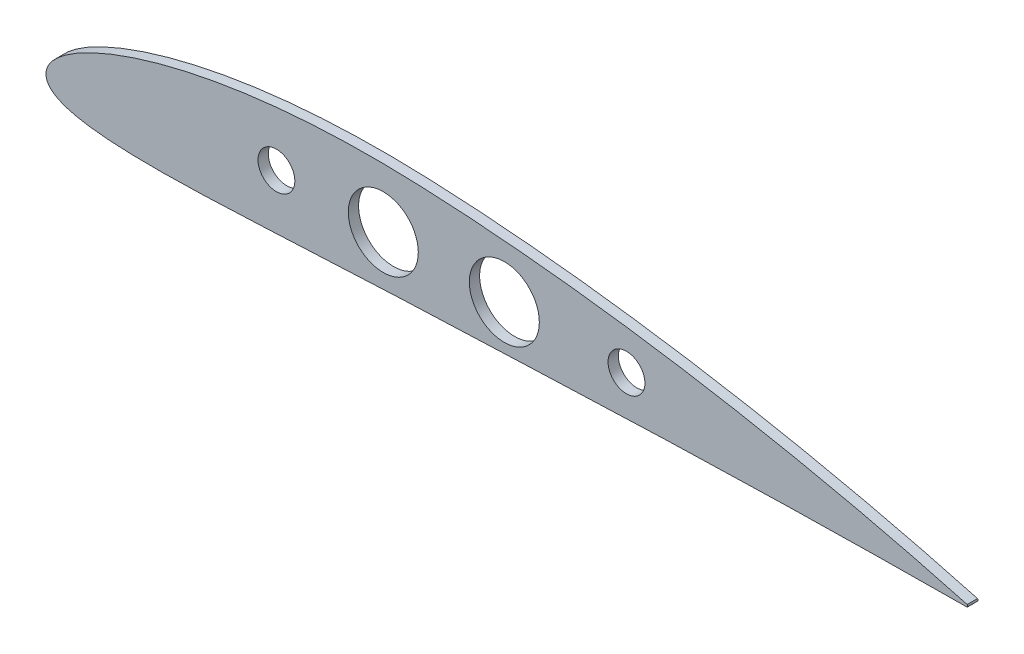
SolidWorks part; units mm, degrees
material "Фанера"
ref_plane "Front Plane" through (0, 0, 0) normal (0, 0, 1) x (1, 0, 0)
ref_plane "Top Plane" through (0, 0, 0) normal (0, 1, 0) x (1, 0, 0)
ref_plane "Right Plane" through (0, 0, 0) normal (1, 0, 0) x (0, 0, -1)
curve "Кривая5"
  spline degree 3 poles (0.048, 0.6214, 0) (0.0227, 0.3735, 0) (-0.0278, -0.1225, 0) (0.078, -0.8844, 0) (0.3497, -1.6388, 0) (0.8143, -2.3651, 0) (1.4635, -3.0393, 0) (2.291, -3.661, 0) (3.3059, -4.2358, 0) (4.5353, -4.7737, 0) (6.0297, -5.2822, 0) (7.869, -5.7653, 0) (10.1688, -6.2217, 0) (13.0754, -6.6396, 0) (16.7281, -6.993, 0) (21.19, -7.2473, 0) (26.4, -7.3766, 0) (32.1974, -7.3763, 0) (38.3978, -7.2614, 0) (44.8576, -7.0566, 0) (51.4865, -6.7865, 0) (58.231, -6.4723, 0) (65.0521, -6.1329, 0) (71.9108, -5.784, 0) (78.7714, -5.4397, 0) (85.6105, -5.111, 0) (92.4321, -4.805, 0) (99.255, -4.532, 0) (106.0974, -4.2783, 0) (112.9692, -4.0031, 0) (119.8644, -3.7232, 0) (126.7739, -3.4401, 0) (133.6816, -3.1587, 0) (140.5819, -2.8824, 0) (147.472, -2.6139, 0) (154.3526, -2.3556, 0) (161.225, -2.1094, 0) (168.0909, -1.8766, 0) (174.9516, -1.6586, 0) (181.8086, -1.4564, 0) (188.6632, -1.2704, 0) (195.5166, -1.1011, 0) (202.3695, -0.9486, 0) (209.2212, -0.8129, 0) (216.0668, -0.6936, 0) (222.8864, -0.5903, 0) (229.6176, -0.5029, 0) (236.0874, -0.4315, 0) (241.9808, -0.3765, 0) (246.559, -0.3395, 0) (249.1205, -0.3213, 0) (250, -0.315, 0) knots 0 0 0 0 0.002941 0.005884 0.009016 0.012365 0.016008 0.020037 0.024574 0.029784 0.035897 0.04324 0.052276 0.063635 0.077983 0.095698 0.11652 0.139661 0.164312 0.189919 0.216157 0.242838 0.269834 0.296993 0.324123 0.351139 0.378036 0.404946 0.431961 0.459078 0.486347 0.513641 0.540929 0.568176 0.59538 0.622543 0.649673 0.676775 0.703855 0.730919 0.757971 0.785018 0.812062 0.839103 0.866132 0.893099 0.919831 0.94581 0.969681 0.98959 1 1 1 1
curve "Кривая6"
  spline degree 3 poles (250, 0.315, 0) (249.1557, 0.545, 0) (246.7202, 1.2085, 0) (242.3913, 2.3583, 0) (236.8498, 3.7876, 0) (230.7799, 5.298, 0) (224.4559, 6.8129, 0) (218.0305, 8.2916, 0) (211.5624, 9.7197, 0) (205.0724, 11.0924, 0) (198.568, 12.4079, 0) (192.0524, 13.6653, 0) (185.5276, 14.8641, 0) (178.9953, 16.0034, 0) (172.4571, 17.0824, 0) (165.9143, 18.0998, 0) (159.3687, 19.0545, 0) (152.8218, 19.9449, 0) (146.2754, 20.7693, 0) (139.7314, 21.5257, 0) (133.1918, 22.212, 0) (126.6587, 22.8257, 0) (120.1368, 23.364, 0) (113.6286, 23.8247, 0) (107.1527, 24.2002, 0) (100.7411, 24.4984, 0) (94.4118, 24.6866, 0) (88.1559, 24.7401, 0) (81.949, 24.6588, 0) (75.7805, 24.441, 0) (69.6537, 24.0819, 0) (63.5754, 23.578, 0) (57.5552, 22.9249, 0) (51.6058, 22.1191, 0) (45.7444, 21.1566, 0) (39.9959, 20.0354, 0) (34.3979, 18.7563, 0) (29.0104, 17.3276, 0) (23.9258, 15.7719, 0) (19.2707, 14.1343, 0) (15.1791, 12.4833, 0) (11.7405, 10.8956, 0) (8.9594, 9.4296, 0) (6.7609, 8.1086, 0) (5.0337, 6.9246, 0) (3.6717, 5.8542, 0) (2.5921, 4.8713, 0) (1.7382, 3.9526, 0) (1.0699, 3.0809, 0) (0.5716, 2.2416, 0) (0.2158, 1.4308, 0) (0.1023, 0.8832, 0) (0.048, 0.6214, 0) knots 0 0 0 0 0.010162 0.029313 0.052012 0.076619 0.101948 0.127526 0.153184 0.178868 0.204558 0.230246 0.255926 0.281594 0.307246 0.332878 0.358485 0.384061 0.409603 0.435104 0.460559 0.485959 0.511303 0.536552 0.561723 0.586629 0.611085 0.635251 0.659272 0.683164 0.706922 0.730536 0.753983 0.777235 0.800246 0.822951 0.845237 0.866916 0.887662 0.906968 0.924203 0.938879 0.950932 0.960693 0.968647 0.975233 0.980795 0.985584 0.989782 0.993521 0.996902 1 1 1 1
sketch "Эскиз1" plane through (0, 0, 0) normal (0, 0, 1) x (1, 0, 0)
  line L0 (250.1305, 0) -> (250.1305, 54.8427) construction
  line L1 (0, 0) -> (0, 70.5199) construction
  line L2 (0, 0) -> (253.0634, 0) construction
  line L3 (62.5326, 62.6361) -> (62.5326, -41.5636) construction
  line L4 (157.5326, 67.9319) -> (157.5326, -57.0034) construction
  line L5 (175.0913, 63.8571) -> (175.0913, -32.3947) construction
  arc A0 (250, 0.315) -> (250, -0.315) centre (249.685, 0) cw
  circle A1 centre (62.5326, 8.5962) radius 5
  circle A2 centre (157.5326, 8.5962) radius 5
  circle A3 centre (91.5326, 8.5962) radius 9.5
  circle A4 centre (124.3816, 8.5962) radius 9.5
  spline S0 degree 3 poles (-1998.9862, 52.2873) (51.3697, 19.9849) (-1.4299, 9.9734) (0.078, -0.8844) (0.3497, -1.6388) (0.8143, -2.3651) (1.4635, -3.0393) (2.291, -3.661) (3.3059, -4.2358) (4.5353, -4.7737) (6.0297, -5.2822) (7.869, -5.7653) (10.1688, -6.2217) (13.0754, -6.6396) (16.7281, -6.993) (21.19, -7.2473) (26.4, -7.3766) (32.1974, -7.3763) (38.3978, -7.2614) (44.8576, -7.0566) (51.4865, -6.7865) (58.231, -6.4723) (65.0521, -6.1329) (71.9108, -5.784) (78.7714, -5.4397) (85.6105, -5.111) (92.4321, -4.805) (99.255, -4.532) (106.0974, -4.2783) (112.9692, -4.0031) (119.8644, -3.7232) (126.7739, -3.4401) (133.6816, -3.1587) (140.5819, -2.8824) (147.472, -2.6139) (154.3526, -2.3556) (161.225, -2.1094) (168.0909, -1.8766) (174.9516, -1.6586) (181.8086, -1.4564) (188.6632, -1.2704) (195.5166, -1.1011) (202.3695, -0.9486) (211.4992, -0.7677) (220.6031, -0.6199) (229.6176, -0.5029) (236.0874, -0.4315) (241.9808, -0.3765) (412.2827, 0.9993) (580.6451, -8.1221) (733.0822, 1918.4656) knots -0.119467 -0.119467 -0.119467 -0.119467 0.002941 0.005884 0.009016 0.012365 0.016008 0.020037 0.024574 0.029784 0.035897 0.04324 0.052276 0.063635 0.077983 0.095698 0.11652 0.139661 0.164312 0.189919 0.216157 0.242838 0.269834 0.296993 0.324123 0.351139 0.378036 0.404946 0.431961 0.459078 0.486347 0.513641 0.540929 0.568176 0.59538 0.622543 0.649673 0.676775 0.703855 0.730919 0.757971 0.785018 0.812062 0.839103 0.893099 0.919831 0.94581 0.969681 0.98959 2.9616 2.9616 2.9616 2.9616 only from (0.048, 0.6214) to (250, -0.315) construction
  spline S1 degree 3 poles (1021.8633, 1838.7787) (414.3615, -64.7736) (332.0293, -21.4512) (242.3913, 2.3583) (236.8498, 3.7876) (230.7799, 5.298) (224.4559, 6.8129) (218.0305, 8.2916) (211.5624, 9.7197) (205.0724, 11.0924) (198.568, 12.4079) (192.0524, 13.6653) (185.5276, 14.8641) (178.9953, 16.0034) (172.4571, 17.0824) (165.9143, 18.0998) (159.3687, 19.0545) (152.8218, 19.9449) (146.2754, 20.7693) (139.7314, 21.5257) (133.1918, 22.212) (126.6587, 22.8257) (120.1368, 23.364) (113.6286, 23.8247) (107.1527, 24.2002) (100.7411, 24.4984) (94.4118, 24.6866) (88.1559, 24.7401) (81.949, 24.6588) (75.7805, 24.441) (69.6537, 24.0819) (63.5754, 23.578) (57.5552, 22.9249) (51.6058, 22.1191) (45.7444, 21.1566) (39.9959, 20.0354) (34.3979, 18.7563) (29.0104, 17.3276) (23.9258, 15.7719) (19.2707, 14.1343) (15.1791, 12.4833) (11.7405, 10.8956) (8.9594, 9.4296) (6.7609, 8.1086) (5.0337, 6.9246) (3.6717, 5.8542) (2.5921, 4.8713) (1.7382, 3.9526) (1.0699, 3.0809) (0.5716, 2.2416) (-4.3308, -8.9285) (41.0506, -34.7699) (-1925.2597, 540.0689) knots -1.025 -1.025 -1.025 -1.025 0.010162 0.029313 0.052012 0.076619 0.101948 0.127526 0.153184 0.178868 0.204558 0.230246 0.255926 0.281594 0.307246 0.332878 0.358485 0.384061 0.409603 0.435104 0.460559 0.485959 0.511303 0.536552 0.561723 0.586629 0.611085 0.635251 0.659272 0.683164 0.706922 0.730536 0.753983 0.777235 0.800246 0.822951 0.845237 0.866916 0.887662 0.906968 0.924203 0.938879 0.950932 0.960693 0.968647 0.975233 0.980795 0.985584 0.989782 0.993521 0.996902 1.130551 1.130551 1.130551 1.130551 only from (250, 0.315) to (0.048, 0.6214) construction
  spline S2 degree 3 poles (0.048, 0.6214) (0.0227, 0.3735) (-0.0278, -0.1225) (0.078, -0.8844) (0.3497, -1.6388) (0.8143, -2.3651) (1.4635, -3.0393) (2.291, -3.661) (3.3059, -4.2358) (4.5353, -4.7737) (6.0297, -5.2822) (7.869, -5.7653) (10.1688, -6.2217) (13.0754, -6.6396) (16.7281, -6.993) (21.19, -7.2473) (26.4, -7.3766) (32.1974, -7.3763) (38.3978, -7.2614) (44.8576, -7.0566) (51.4865, -6.7865) (58.231, -6.4723) (65.0521, -6.1329) (71.9108, -5.784) (78.7714, -5.4397) (85.6105, -5.111) (92.4321, -4.805) (99.255, -4.532) (106.0974, -4.2783) (112.9692, -4.0031) (119.8644, -3.7232) (126.7739, -3.4401) (133.6816, -3.1587) (140.5819, -2.8824) (147.472, -2.6139) (154.3526, -2.3556) (161.225, -2.1094) (168.0909, -1.8766) (174.9516, -1.6586) (181.8086, -1.4564) (188.6632, -1.2704) (195.5166, -1.1011) (202.3695, -0.9486) (211.4992, -0.7677) (220.6031, -0.6199) (229.6176, -0.5029) (236.0874, -0.4315) (241.9808, -0.3765) (246.559, -0.3395) (249.1205, -0.3213) (250, -0.315) knots 0 0 0 0 0.002941 0.005884 0.009016 0.012365 0.016008 0.020037 0.024574 0.029784 0.035897 0.04324 0.052276 0.063635 0.077983 0.095698 0.11652 0.139661 0.164312 0.189919 0.216157 0.242838 0.269834 0.296993 0.324123 0.351139 0.378036 0.404946 0.431961 0.459078 0.486347 0.513641 0.540929 0.568176 0.59538 0.622543 0.649673 0.676775 0.703855 0.730919 0.757971 0.785018 0.812062 0.839103 0.893099 0.919831 0.94581 0.969681 0.98959 1 1 1 1
  spline S3 degree 3 poles (250, 0.315) (249.1557, 0.545) (246.7202, 1.2085) (242.3913, 2.3583) (236.8498, 3.7876) (230.7799, 5.298) (224.4559, 6.8129) (218.0305, 8.2916) (211.5624, 9.7197) (205.0724, 11.0924) (198.568, 12.4079) (192.0524, 13.6653) (185.5276, 14.8641) (178.9953, 16.0034) (172.4571, 17.0824) (165.9143, 18.0998) (159.3687, 19.0545) (152.8218, 19.9449) (146.2754, 20.7693) (139.7314, 21.5257) (133.1918, 22.212) (126.6587, 22.8257) (120.1368, 23.364) (113.6286, 23.8247) (107.1527, 24.2002) (100.7411, 24.4984) (94.4118, 24.6866) (88.1559, 24.7401) (81.949, 24.6588) (75.7805, 24.441) (69.6537, 24.0819) (63.5754, 23.578) (57.5552, 22.9249) (51.6058, 22.1191) (45.7444, 21.1566) (39.9959, 20.0354) (34.3979, 18.7563) (29.0104, 17.3276) (23.9258, 15.7719) (19.2707, 14.1343) (15.1791, 12.4833) (11.7405, 10.8956) (8.9594, 9.4296) (6.7609, 8.1086) (5.0337, 6.9246) (3.6717, 5.8542) (2.5921, 4.8713) (1.7382, 3.9526) (1.0699, 3.0809) (0.5716, 2.2416) (0.2158, 1.4308) (0.1023, 0.8832) (0.048, 0.6214) knots 0 0 0 0 0.010162 0.029313 0.052012 0.076619 0.101948 0.127526 0.153184 0.178868 0.204558 0.230246 0.255926 0.281594 0.307246 0.332878 0.358485 0.384061 0.409603 0.435104 0.460559 0.485959 0.511303 0.536552 0.561723 0.586629 0.611085 0.635251 0.659272 0.683164 0.706922 0.730536 0.753983 0.777235 0.800246 0.822951 0.845237 0.866916 0.887662 0.906968 0.924203 0.938879 0.950932 0.960693 0.968647 0.975233 0.980795 0.985584 0.989782 0.993521 0.996902 1 1 1 1
  point P20 (91.7243, 8.5962)
  point P21 (91.1297, 8.5962)
  point P22 (62.5326, 23.4501)
  point P23 (62.5326, -6.2577)
  point P28 (124.3816, 8.5962)
  point P29 (0, 0)
  point P32 (123.7495, 7.7978)
  dimension "D3" = 10
  dimension "D8" = 19
  dimension "D1" = 250.1305
  dimension "D2" = 62.5326
  dimension "D4" = 95
  dimension "D5" = 75.0391
  dimension "D6" = 29.7079
  dimension "D7" = 14.8539
  dimension "D9" = 61.849
  dimension "D10" = 29
extrude "Бобышка-Вытянуть1" add sketch "Эскиз1" along normal mid plane 2.8
equation "\"D2@Эскиз1\"=\"D1@Эскиз1\"/4"
equation "\"D7@Эскиз1\"=\"D6@Эскиз1\"/2"
equation "\"D5@Эскиз1\"=\"D1@Эскиз1\"*0.3"
